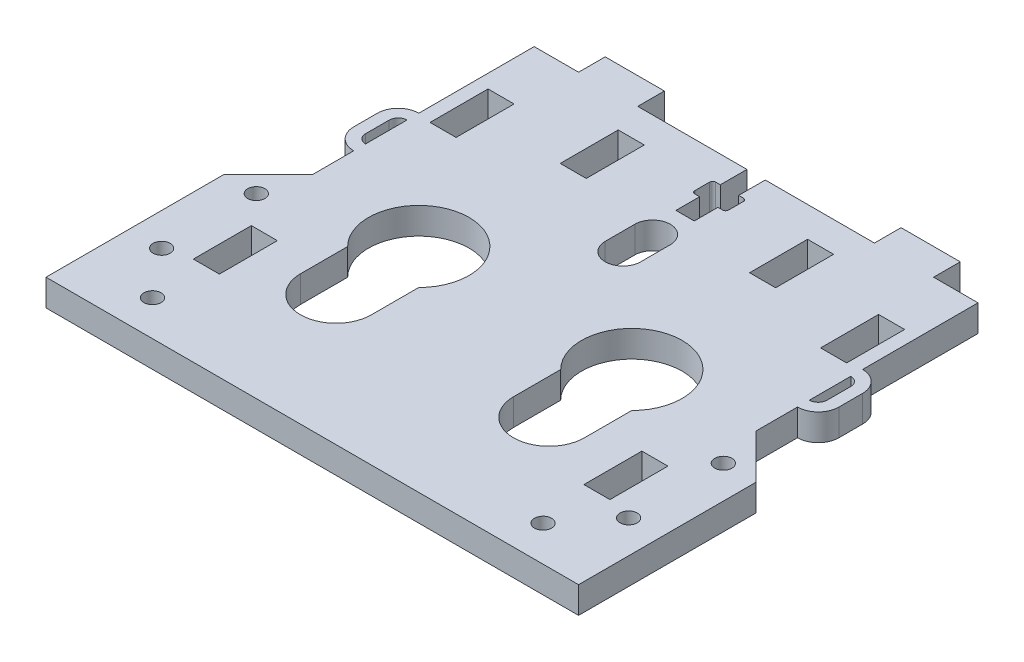
SolidWorks part; units mm, degrees
ref_plane "Front Plane" through (0, 0, 0) normal (0, 0, 1) x (1, 0, 0)
ref_plane "Top Plane" through (0, 0, 0) normal (0, 1, 0) x (1, 0, 0)
ref_plane "Right Plane" through (0, 0, 0) normal (1, 0, 0) x (0, 0, -1)
sketch "Sketch1" plane through (0, 0, 0) normal (0, 1, 0) x (1, 0, 0)
  line L1 (-37.5, 37.5) -> (37.5, 37.5)
  line L2 (-37.5, 37.5) -> (-37.5, -37.5)
  line L3 (-37.5, -37.5) -> (37.5, -37.5)
  line L4 (37.5, 37.5) -> (37.5, -37.5)
  line L5 (-37.5, 37.5) -> (37.5, -37.5) construction
  line L6 (-37.5, -37.5) -> (37.5, 37.5) construction
  point P0 (0, 0)
  dimension "D1" = 75
  dimension "D2" = 75
extrude "MainShape" add sketch "Sketch1" along normal blind 4.5
sketch "Sketch2" plane through (0, 4.5, 0) normal (0, 1, 0) x (1, 0, 0)
  line L0 (0, -37.5) -> (0, 37.5) construction
  line L1 (-37.5, -37.5) -> (37.5, -37.5) construction
  line L2 (37.5, 37.5) -> (-37.5, 37.5) construction
  line L4 (-5, 42) -> (5, 42)
  line L5 (-5, 42) -> (-5, 33)
  line L6 (-5, 33) -> (5, 33)
  line L7 (5, 42) -> (5, 33)
  line L8 (-5, 42) -> (5, 33) construction
  line L9 (-5, 33) -> (5, 42) construction
  dimension "D1" = 10
  dimension "D2" = 4.5
extrude "Tab1" [suppressed] add sketch "Sketch2" against normal through all
sketch "Sketch4" [suppressed] plane through (0, 4.5, 0) normal (0, 1, 0) x (1, 0, 0)
  line L0 (0, 42) -> (0, -37.5) construction
  line L1 (5, 42) -> (-5, 42) construction
  line L2 (-47.5, -37.5) -> (47.5, -37.5) construction
  line L3 (-40, 37.5) -> (-40, 27) construction
  line L4 (-5, 37.5) -> (-47.5, 37.5) construction
  line L5 (-38.25, 27) -> (-41.75, 27) construction
  line L6 (-41.75, 27) -> (-41.75, 37.5) construction
  line L7 (-38.25, 27) -> (-41.75, 27)
  line L8 (-41.75, 27) -> (-41.75, 29.5)
  line L9 (-41.75, 29.5) -> (-42.75, 29.5)
  line L10 (-43, 29.75) -> (-43, 33.45)
  line L11 (-42.75, 33.7) -> (-41.75, 33.7)
  line L12 (-41.75, 33.7) -> (-41.75, 37.5)
  line L13 (-41.75, 37.5) -> (-38.25, 37.5)
  line L14 (-38.25, 27) -> (-38.25, 37.5) construction
  line L15 (-38.25, 33.7) -> (-38.25, 37.5)
  line L16 (-37.25, 33.7) -> (-38.25, 33.7)
  line L17 (-37, 29.75) -> (-37, 33.45)
  line L18 (-38.25, 29.5) -> (-37.25, 29.5)
  line L19 (-38.25, 27) -> (-38.25, 29.5)
  line L20 (38.25, 27) -> (38.25, 37.5) construction
  line L21 (41.75, 27) -> (41.75, 37.5) construction
  line L22 (38.25, 27) -> (41.75, 27) construction
  line L23 (40, 37.5) -> (40, 27) construction
  line L24 (38.25, 27) -> (38.25, 29.5)
  line L25 (38.25, 29.5) -> (37.25, 29.5)
  line L26 (37, 29.75) -> (37, 33.45)
  line L27 (37.25, 33.7) -> (38.25, 33.7)
  line L28 (38.25, 33.7) -> (38.25, 37.5)
  line L29 (41.75, 37.5) -> (38.25, 37.5)
  line L30 (41.75, 33.7) -> (41.75, 37.5)
  line L31 (42.75, 33.7) -> (41.75, 33.7)
  line L32 (43, 29.75) -> (43, 33.45)
  line L33 (41.75, 29.5) -> (42.75, 29.5)
  line L34 (41.75, 27) -> (41.75, 29.5)
  line L35 (38.25, 27) -> (41.75, 27)
  arc A0 (-42.75, 29.5) -> (-43, 29.75) centre (-42.75, 29.75) cw
  arc A1 (-37, 29.75) -> (-37.25, 29.5) centre (-37.25, 29.75) cw
  arc A2 (-37.25, 33.7) -> (-37, 33.45) centre (-37.25, 33.45) cw
  arc A3 (-43, 33.45) -> (-42.75, 33.7) centre (-42.75, 33.45) cw
  arc A4 (43, 33.45) -> (42.75, 33.7) centre (42.75, 33.45) ccw
  arc A5 (37.25, 33.7) -> (37, 33.45) centre (37.25, 33.45) ccw
  arc A6 (37, 29.75) -> (37.25, 29.5) centre (37.25, 29.75) ccw
  arc A7 (42.75, 29.5) -> (43, 29.75) centre (42.75, 29.75) ccw
  point P24 (-43, 29.5)
  point P27 (-37, 29.5)
  point P30 (-37, 33.7)
  point P33 (-43, 33.7)
  point P56 (43, 33.7)
  point P57 (37, 33.7)
  point P58 (37, 29.5)
  point P59 (43, 29.5)
  dimension "D7" = 0.5
  dimension "D1" = 11
  dimension "D2" = 1.55
  dimension "D3" = 3.5
  dimension "D4" = 2.85
  dimension "D5" = 8
  dimension "D6" = 40
extrude "Cut-Extrude2" [suppressed] cut sketch "Sketch4" against normal through all
sketch "Sketch5" plane through (0, 4.5, 0) normal (0, 1, 0) x (1, 0, 0)
  line L0 (0, -37.5) -> (0, 37.5) construction
  line L1 (-37.5, -37.5) -> (37.5, -37.5) construction
  line L3 (33, 37.5) -> (33, -37.5) construction
  line L4 (37.5, 37.5) -> (-37.5, 37.5) construction
  line L5 (-33, 37.5) -> (-33, -37.5) construction
  line L6 (30.8, 27.4) -> (35.2, 27.4)
  line L7 (30.8, 27.4) -> (30.8, 17.6)
  line L8 (30.8, 17.6) -> (35.2, 17.6)
  line L9 (35.2, 27.4) -> (35.2, 17.6)
  line L10 (30.8, 27.4) -> (35.2, 17.6) construction
  line L11 (30.8, 17.6) -> (35.2, 27.4) construction
  line L12 (-30.8, 17.6) -> (-35.2, 27.4) construction
  line L13 (-30.8, 27.4) -> (-35.2, 17.6) construction
  line L14 (-35.2, 27.4) -> (-35.2, 17.6)
  line L15 (-30.8, 17.6) -> (-35.2, 17.6)
  line L16 (-30.8, 27.4) -> (-30.8, 17.6)
  line L17 (-30.8, 27.4) -> (-35.2, 27.4)
  line L18 (-37.5, 2.5) -> (37.5, 2.5) construction
  line L19 (-37.5, 37.5) -> (-37.5, -37.5) construction
  line L20 (37.5, -37.5) -> (37.5, 37.5) construction
  line L21 (-30.8, -22.4) -> (-35.2, -12.6) construction
  line L22 (-30.8, -12.6) -> (-35.2, -22.4) construction
  line L23 (30.8, -12.6) -> (35.2, -22.4) construction
  line L24 (30.8, -22.4) -> (35.2, -12.6) construction
  line L25 (-30.8, -22.4) -> (-35.2, -22.4)
  line L26 (-30.8, -22.4) -> (-30.8, -12.6)
  line L27 (-30.8, -12.6) -> (-35.2, -12.6)
  line L28 (-35.2, -22.4) -> (-35.2, -12.6)
  line L29 (35.2, -22.4) -> (35.2, -12.6)
  line L30 (30.8, -12.6) -> (35.2, -12.6)
  line L31 (30.8, -22.4) -> (30.8, -12.6)
  line L32 (30.8, -22.4) -> (35.2, -22.4)
  line L33 (-30.8, 27.4) -> (-35.2, 17.6) construction
  line L34 (-37.5, 37.5) -> (37.5, 37.5) construction
  line L35 (37.5, 37.5) -> (-37.5, 37.5) construction
  point P10 (33, 22.5)
  point P21 (-33, 22.5)
  point P36 (-33, -17.5)
  point P37 (33, -17.5)
  dimension "D1" = 33
  dimension "D2" = 9.8
  dimension "D3" = 4.4
  dimension "D4" = 15
  dimension "D5" = 40
extrude "Cut-Extrude3" cut sketch "Sketch5" against normal through all
sketch "Sketch6" plane through (0, 4.5, 0) normal (0, 1, 0) x (1, 0, 0)
  line L0 (-18, -37.5) -> (-18, 28) construction
  line L1 (-24, -15.5) -> (-24, -7.5208)
  line L3 (-37.5, -15.5) -> (37.5, -15.5) construction
  line L4 (-37.5, 37.5) -> (-37.5, -37.5) construction
  line L5 (37.5, -37.5) -> (37.5, 37.5) construction
  line L6 (37.5, 37.5) -> (-37.5, 37.5) construction
  line L7 (-37.5, -37.5) -> (37.5, -37.5) construction
  line L8 (-12, -15.5) -> (-12, -7.5208)
  line L9 (-37.5, 37.5) -> (37.5, 37.5) construction
  arc A0 (-24, -15.5) -> (-12, -15.5) centre (-18, -15.5) ccw
  arc A2 (-12, -7.5208) -> (-24, -7.5208) centre (-18, -1.5) ccw
  dimension "D1" = 12
  dimension "D6" = 8.5
  dimension "D2" = 53
  dimension "D3" = 0
  dimension "D5" = 0
  dimension "D7" = 14
  dimension "D4" = 18
extrude "Cut-Extrude4" cut sketch "Sketch6" against normal through all
sketch "Sketch13" plane through (0, 4.5, 0) normal (0, 1, 0) x (1, 0, 0)
  line L0 (-37.5, 0) -> (-45, -7.5)
  line L1 (-37.5, 37.5) -> (-37.5, -37.5) construction
  line L2 (-45, -7.5) -> (-45, -37.5)
  line L3 (-45, -37.5) -> (-37.5, -37.5)
  line L4 (-37.5, -37.5) -> (-37.5, 0)
  line L5 (0, 37.5) -> (0, -37.5) construction
  line L6 (37.5, 37.5) -> (-37.5, 37.5) construction
  line L7 (-37.5, -37.5) -> (37.5, -37.5) construction
  line L8 (37.5, -37.5) -> (37.5, 0)
  line L9 (45, -37.5) -> (37.5, -37.5)
  line L10 (45, -7.5) -> (45, -37.5)
  line L11 (37.5, 0) -> (45, -7.5)
  line L12 (-37.5, -37.5) -> (-37.5, 0)
  line M23 (37.5, -37.5) -> (37.5, 37.5)
  line M25 (-37.5, 37.5) -> (-37.5, -37.5)
  dimension "D1" = 45
  dimension "D2" = 30
extrude "Boss-Extrude2" add sketch "Sketch13" against normal through all contours L2 L3 L0 M25 | L11 L9 L10 M23 region at (-41.1111, 4.5, 20.5556) region at (41.1111, 4.5, 20.5556)
sketch "Sketch8" plane through (0, 4.5, 0) normal (0, 1, 0) x (1, 0, 0)
  line L0 (-18, -9.5) -> (-18, -21.5) construction
  line L1 (-18, -15.5) -> (-39.46, -15.5) construction
  line L2 (-39.46, -23.5) -> (-39.46, -7.5) construction
  line L3 (-18, -21.5) -> (-18, -9.5) construction
  circle A0 centre (-39.46, -7.5) radius 1.45
  circle A1 centre (-18, -15.5) radius 6 construction
  circle A2 centre (-39.46, -23.5) radius 1.45
  dimension "D3" = 2.9
  dimension "D1" = 0
  dimension "D2" = 8
  dimension "D4" = 21.46
extrude "Cut-Extrude6" cut sketch "Sketch8" against normal through all
mirror "Mirror1" about plane through (0, 0, 0) normal (1, 0, 0) of "Cut-Extrude6", "Cut-Extrude4"
sketch "Sketch11" plane through (0, 4.5, 0) normal (0, 1, 0) x (1, 0, 0)
  line L0 (0, 37.5) -> (0, -37.5) construction
  line L1 (37.5, 37.5) -> (-37.5, 37.5) construction
  line L2 (-45, -37.5) -> (45, -37.5) construction
  line L3 (-25, 42) -> (-25, 37.5) construction
  line L4 (-30, 37.5) -> (-20, 37.5)
  line L5 (-30, 37.5) -> (-30, 42)
  line L6 (-30, 42) -> (-20, 42)
  line L7 (-20, 37.5) -> (-20, 42)
  line L8 (25, 42) -> (25, 37.5) construction
  line L9 (20, 37.5) -> (20, 42)
  line L10 (30, 42) -> (20, 42)
  line L11 (30, 37.5) -> (30, 42)
  line L12 (30, 37.5) -> (20, 37.5)
  dimension "D1" = 10
  dimension "D2" = 4.5
  dimension "D3" = 25
extrude "RearTabs" add sketch "Sketch11" against normal through all
sketch "Sketch12" plane through (0, 4.5, 0) normal (0, 1, 0) x (1, 0, 0)
  line L0 (0, 0) -> (0, 37.5) construction
  line L1 (20, 37.5) -> (-20, 37.5) construction
  line L2 (1.55, 37.5) -> (-1.55, 37.5)
  line L3 (-1.55, 37.5) -> (-1.55, 33)
  line L4 (-1.55, 33) -> (-2.35, 33)
  line L5 (-2.85, 32.5) -> (-2.85, 30)
  line L6 (-2.35, 29.5) -> (-1.55, 29.5)
  line L7 (-1.55, 29.5) -> (-1.55, 25.5)
  line L8 (-1.55, 25.5) -> (1.55, 25.5)
  line L9 (1.55, 29.5) -> (1.55, 25.5)
  line L10 (2.35, 29.5) -> (1.55, 29.5)
  line L11 (2.85, 32.5) -> (2.85, 30)
  line L12 (1.55, 33) -> (2.35, 33)
  line L13 (1.55, 37.5) -> (1.55, 33)
  arc A0 (-2.85, 30) -> (-2.35, 29.5) centre (-2.35, 30) ccw
  arc A1 (-2.35, 33) -> (-2.85, 32.5) centre (-2.35, 32.5) ccw
  arc A2 (2.35, 33) -> (2.85, 32.5) centre (2.35, 32.5) cw
  arc A3 (2.85, 30) -> (2.35, 29.5) centre (2.35, 30) cw
  point P14 (-2.85, 29.5)
  point P17 (-2.85, 33)
  point P25 (0, 25.5)
  point P28 (2.85, 33)
  point P29 (2.85, 29.5)
  dimension "D5" = 8
  dimension "D1" = 12
  dimension "D6" = 0.5
  dimension "D2" = 3.5
  dimension "D3" = 2.85
  dimension "D4" = 1.55
extrude "FrontScrewSlot" cut sketch "Sketch12" against normal through all
sketch "Sketch14" plane through (0, 4.5, 0) normal (0, 1, 0) x (1, 0, 0)
  line L0 (-33, 27.4) -> (-33, -37.5) construction
  line L1 (-30.8, 27.4) -> (-35.2, 27.4) construction
  line L2 (-45, -37.5) -> (45, -37.5) construction
  line L3 (-30, 37.5) -> (-37.5, 37.5) construction
  line L4 (0, 0) -> (0, -37.5) construction
  line L5 (33, 27.4) -> (33, -37.5) construction
  line L6 (-33, 27.4) -> (-33, -37.5) construction
  circle A0 centre (-33, -31.5) radius 1.45
  circle A1 centre (33, -31.5) radius 1.45
  dimension "D2" = 2.9
  dimension "D1" = 69
extrude "BraceScrews" cut sketch "Sketch14" against normal through all
sketch "Sketch15" plane through (0, 4.5, 0) normal (0, 1, 0) x (1, 0, 0)
  line L0 (0, -37.5) -> (0, 25.5) construction
  line L1 (-45, -37.5) -> (45, -37.5) construction
  line L2 (-1.55, 25.5) -> (1.55, 25.5) construction
  line L3 (16, 27.5) -> (-16, 27.5) construction
  line L4 (-1.55, 37.5) -> (-20, 37.5) construction
  line L5 (-18.2, 32.4) -> (-13.8, 32.4)
  line L6 (-18.2, 32.4) -> (-18.2, 22.6)
  line L7 (-18.2, 22.6) -> (-13.8, 22.6)
  line L8 (-13.8, 32.4) -> (-13.8, 22.6)
  line L9 (-18.2, 32.4) -> (-13.8, 22.6) construction
  line L10 (-18.2, 22.6) -> (-13.8, 32.4) construction
  line L11 (18.2, 22.6) -> (13.8, 32.4) construction
  line L12 (18.2, 32.4) -> (13.8, 22.6) construction
  line L13 (13.8, 32.4) -> (13.8, 22.6)
  line L14 (18.2, 22.6) -> (13.8, 22.6)
  line L15 (18.2, 32.4) -> (18.2, 22.6)
  line L16 (18.2, 32.4) -> (13.8, 32.4)
  point P19 (0, 27.5)
  dimension "D1" = 16
  dimension "D2" = 4.4
  dimension "D3" = 9.8
  dimension "D4" = 10
extrude "FanTabs" cut sketch "Sketch15" against normal through all
sketch "Sketch16" plane through (0, 4.5, 0) normal (0, 1, 0) x (1, 0, 0)
  line L0 (0, 0) -> (0, 25.5) construction
  line L1 (-1.55, 25.5) -> (1.55, 25.5) construction
  line L2 (0, 20) -> (0, 15) construction
  line L3 (3, 20) -> (3, 15)
  line L4 (-3, 20) -> (-3, 15)
  arc A0 (3, 20) -> (-3, 20) centre (0, 20) ccw
  arc A1 (-3, 15) -> (3, 15) centre (0, 15) ccw
  point P7 (0, 17.5)
  dimension "D1" = 3
  dimension "D2" = 20
  dimension "D3" = 5
extrude "WiringSlot" cut sketch "Sketch16" against normal through all
sketch "Sketch17" plane through (0, 4.5, 0) normal (0, 1, 0) x (1, 0, 0)
  line L0 (-37.5, 14.5) -> (-37.5, 10.5) construction
  line L3 (-37.5, 37.5) -> (-37.5, 0) construction
  line L4 (-36, 14.5) -> (-36, 10.5)
  line L5 (-39, 14.5) -> (-39, 10.5)
  line L6 (-37.5, 14.5) -> (-37.5, 10.5) construction
  line L7 (-34, 14.5) -> (-34, 10.5)
  line L8 (-41, 14.5) -> (-41, 10.5)
  line L9 (-41, 12.5) -> (-37.5, 12.5) construction
  line L10 (0, 0) -> (0, -12.1805) construction
  arc A0 (-36, 14.5) -> (-39, 14.5) centre (-37.5, 14.5) ccw
  arc A1 (-39, 10.5) -> (-36, 10.5) centre (-37.5, 10.5) ccw
  arc A2 (-34, 14.5) -> (-41, 14.5) centre (-37.5, 14.5) ccw
  arc A3 (-41, 10.5) -> (-34, 10.5) centre (-37.5, 10.5) ccw
  point P4 (-37.5, 12.5)
  point P10 (-37.5, 12.5)
  dimension "D4" = 4
  dimension "D5" = 25
  dimension "D1" = 0
  dimension "D2" = 2
  dimension "D3" = 1.5
extrude "Boss-Extrude3" add sketch "Sketch17" against normal through all
mirror "Mirror2" about plane through (0, 0, 0) normal (1, 0, 0) of "Boss-Extrude3"
equation "\"X-ROD-SPACING\"=45"
equation "\"Y-ROD-SPACING\"=75"
equation "\"Z-ROD-SPACING\"=17.5"
equation "\"Y-BED-OFFSET\"=2"
equation "\"Y-BED-ROD-INSET\"=3.5"
equation "\"Y-BED-SCREW-SPACING\"=209"
equation "\"Y-BED-SCREW-CUTOUT-SLOT-HEIGHT\"=2"
equation "\"T-SLOT-NUT-FILLET-RADIUS\"=0.5"
equation "\"T-SLOT-SCREW-SHAFT-RADIUS\"=1.55"
equation "\"T-SLOT-SCREW-SHAFT-CUTOUT-LENGTH\"=11.0"
equation "\"T-SLOT-NUT-DEPTH\"=3.5"
equation "\"T-SLOT-NUT-WIDTH\"=2.85"
equation "\"T-SLOT-NUT-END-DISTANCE\"=8"
equation "\"ACRYLIC-THICKNESS\"=10"
equation "\"ACRYLIC-THICKNESS2\"=4.5"
equation "\"ACRYLIC-TAB-CUTOUT-SIZE\"=\"ACRYLIC-THICKNESS\"+\"ACRYLIC-TAB-TOLERANCE\"*2"
equation "\"ACRYLIC-TAB-WIDTH\"=\"ACRYLIC-THICKNESS\""
equation "\"ACRYLIC-M3-HOLE\"=2.9"
equation "\"SMOOTHROD-CAP-SCREW-DISTANCE\"=20"
equation "\"FRAME-WIDTH-INNER\"=370"
equation "\"NEMA17-HOLE-SPACING\"=31"
equation "\"NEMA17-CENTRAL-CUTOUT\"=22.5"
equation "\"Z-BRACKET-REACH\"=55"
equation "\"Z-ROD-INSET\"=16"
equation "\"TOP-BRACKET-SPACING\"=40"
equation "\"SMOOTHROD-X-LENGTH\"=350"
equation "\"SMOOTHROD-Y-LENGTH\"=350"
equation "\"SMOOTHROD-Z-LENGTH\"=350"
equation "\"SMOOTHROD-TIGHTENING-HEADROOM\"=.25"
equation "\"LEADSCREW-Z-LENGTH\"=300"
equation "\"SCREW-LENGTH-FRAME\"=\"ACRYLIC-THICKNESS\" + 10"
equation "\"SCREW-LENGTH-MOTOR\"=\"ACRYLIC-THICKNESS\" + 5"
equation "\"SCREW-LENGTH-EXTRUDER\"=28"
equation "\"SCREW-HEAD-RADIUS\"=6"
equation "\"PRINTED-X-SMOOTHROD-DIAMETER\"=8.4"
equation "\"PRINTED-X-SMOOTHROD-CUTOUT\"=10"
equation "\"PRINTED-X-BASE-HEIGHT\"=10"
equation "\"PRINTED-LM8UU-CUTOUT-SIZE\"=15.5"
equation "\"PRINTED-LM8UU-CUTOUT-LENGTH\"=24.5"
equation "\"PRINTED-X-IDLER-HEIGHT\"=16"
equation "\"PSU-MOUNTING-WIDTH\"=95"
equation "\"PSU-MOUNTING-HEIGHT\"=177"
equation "\"Y-BELT-TO-ROD-DISTANCE\"=20"
equation "\"SPOOL-HOLDER-ROD-SPACING\"=150"
equation "\"ACRYLIC-X-CARRIAGE-WIDTH\"=55"
equation "\"ACRYLIC-X-CARRIAGE-HEIGHT\"=75"
equation "\"ACRYLIC-X-CARRIAGE-SCREW-SPACING-X\"=15"
equation "\"ACRYLIC-X-CARRIAGE-SCREW-SPACING-Y\"=33"
equation "\"ACRYLIC-X-CARRIAGE-CENTER-TAB-SPACING\"=14"
equation "\"D1@MainShape\" = \"ACRYLIC-THICKNESS2\""
equation "\"D1@Sketch2\"=\"ACRYLIC-TAB-WIDTH\""
equation "\"D2@Sketch2\"=\"ACRYLIC-THICKNESS2\""
equation "\"D1@Sketch4\"=\"T-SLOT-SCREW-SHAFT-CUTOUT-LENGTH\""
equation "\"D2@Sketch4\"=\"T-SLOT-SCREW-SHAFT-RADIUS\""
equation "\"D3@Sketch4\"=\"T-SLOT-NUT-DEPTH\""
equation "\"D4@Sketch4\"=\"T-SLOT-NUT-WIDTH\""
equation "\"D5@Sketch4\"=\"T-SLOT-NUT-END-DISTANCE\""
equation "\"D7@Sketch4\"=\"T-SLOT-NUT-FILLET-RADIUS\""
equation "\"ACRYLIC-X-CARRIAGE-EXTRUDER-SHELF-DEPTH\"=\"ACRYLIC-X-CARRIAGE-EXTRUDER-OFFSET\" + 28"
equation "\"ACRYLIC-X-CARRIAGE-LM8UU-CUTOUT-WIDTH\"=24.25"
equation "\"ACRYLIC-X-CARRIAGE-EXTRUDER-BRACE-SPACING\"=23"
equation "\"ACRYLIC-X-CARRIAGE-EXTRUDER-BRACE-TAB-OFFSET\"=20"
equation "\"ACRYLIC-X-CARRIAGE-EXTRUDER-BRACE-HEIGHT\"=35"
equation "\"ACRYLIC-X-CARRIAGE-EXTRUDER-BRACE-SCREW-SPACING\"=22"
equation "\"D2@Sketch5\"=\"ACRYLIC-THICKNESS2-TAB-CUTOUT-HEIGHT\""
equation "\"D3@Sketch5\"=\"ACRYLIC-THICKNESS2-TAB-CUTOUT-WIDTH\""
equation "\"D3@Sketch8\"=\"ACRYLIC-M3-HOLE\""
equation "\"ACRYLIC-X-CARRIAGE-EXTRUDER-ANGLE\"=90"
equation "\"ACRYLIC-X-CARRIAGE-EXTRUDER-OFFSET\"=26"
equation "\"ACRYLIC-TAB-TOLERANCE\"=-.05"
equation "\"ACRYLIC-X-CARRIAGE-DUAL-WIDTH-MULTIPLIER\"=1.65"
equation "\"ACRYLIC-X-CARRIAGE-DUAL-HOTEND-SPACING\"=42"
equation "\"ACRYLIC-X-CARRIAGE-DUAL-WIDTH\"=75"
equation "\"ACRYLIC-X-CARRIAGE-DUAL-HOTEND-SEPARATION\"=36"
equation "\"ACRYLIC-X-CARRIAGE-DUAL-MOUNT-PLATE-DEPTH\"=75"
equation "\"ACRYLIC-X-CARRIAGE-DUAL-MOUNT-BRACE-WIDTH\"=33"
equation "\"D1@Sketch5\"=\"ACRYLIC-X-CARRIAGE-DUAL-MOUNT-BRACE-WIDTH\""
equation "\"ACRYLIC-X-CARRIAGE-DUAL-MOUNT-SCREW-WIDTH\"=40"
equation "\"D6@Sketch4\"=\"ACRYLIC-X-CARRIAGE-DUAL-MOUNT-SCREW-WIDTH\""
equation "\"D1@Sketch1\"=\"ACRYLIC-X-CARRIAGE-DUAL-WIDTH\""
equation "\"D2@Sketch1\"=\"ACRYLIC-X-CARRIAGE-DUAL-MOUNT-PLATE-DEPTH\""
equation "\"D4@Sketch6\"=\"ACRYLIC-X-CARRIAGE-DUAL-HOTEND-SEPARATION\"/2"
equation "\"D1@Sketch11\"=\"ACRYLIC-TAB-WIDTH\""
equation "\"D2@Sketch11\"=\"ACRYLIC-THICKNESS2\""
equation "\"D1@Sketch12\"=\"T-SLOT-SCREW-SHAFT-CUTOUT-LENGTH\"+1"
equation "\"D2@Sketch12\"=\"T-SLOT-NUT-DEPTH\""
equation "\"D3@Sketch12\"=\"T-SLOT-NUT-WIDTH\""
equation "\"D4@Sketch12\"=\"T-SLOT-SCREW-SHAFT-RADIUS\""
equation "\"D5@Sketch12\"=\"T-SLOT-NUT-END-DISTANCE\""
equation "\"D6@Sketch12\"=\"T-SLOT-NUT-FILLET-RADIUS\""
equation "\"D2@Sketch14\"=\"ACRYLIC-M3-HOLE\""
equation "\"D2@Sketch15\"=\"ACRYLIC-THICKNESS2-TAB-CUTOUT-WIDTH\""
equation "\"D3@Sketch15\"=\"ACRYLIC-THICKNESS2-TAB-CUTOUT-HEIGHT\""
equation "\"KERF\"=0.05"
equation "\"PRINTED-M3-HOLE\"=3.5"
equation "\"PRINTED-M3-NUT-AF\"=6.25"
equation "\"ACRYLIC-X-CARRIAGE-LM8UU-CUTOUT-HEIGHT\"=11.0"
equation "\"ACRYLIC-X-CARRIAGE-DUAL-FAN-OFFSET\"=52"
equation "\"ACRYLIC-X-CARRIAGE-DUAL-FAN-HEIGHT\"=20"
equation "\"BLOWER-FAN-WIDTH\"=15"
equation "\"ACRYLIC-THICKNESS-TAB-CUTOUT-WIDTH\"=\"ACRYLIC-THICKNESS\"-\"KERF\"*2"
equation "\"ACRYLIC-THICKNESS-TAB-CUTOUT-HEIGHT\"=\"ACRYLIC-TAB-WIDTH\"-\"KERF\"*4"
equation "\"ACRYLIC-THICKNESS2-TAB-CUTOUT-WIDTH\"=\"ACRYLIC-THICKNESS2\"-\"KERF\"*2"
equation "\"ACRYLIC-THICKNESS2-TAB-CUTOUT-HEIGHT\"=\"ACRYLIC-TAB-WIDTH\"-\"KERF\"*4"
